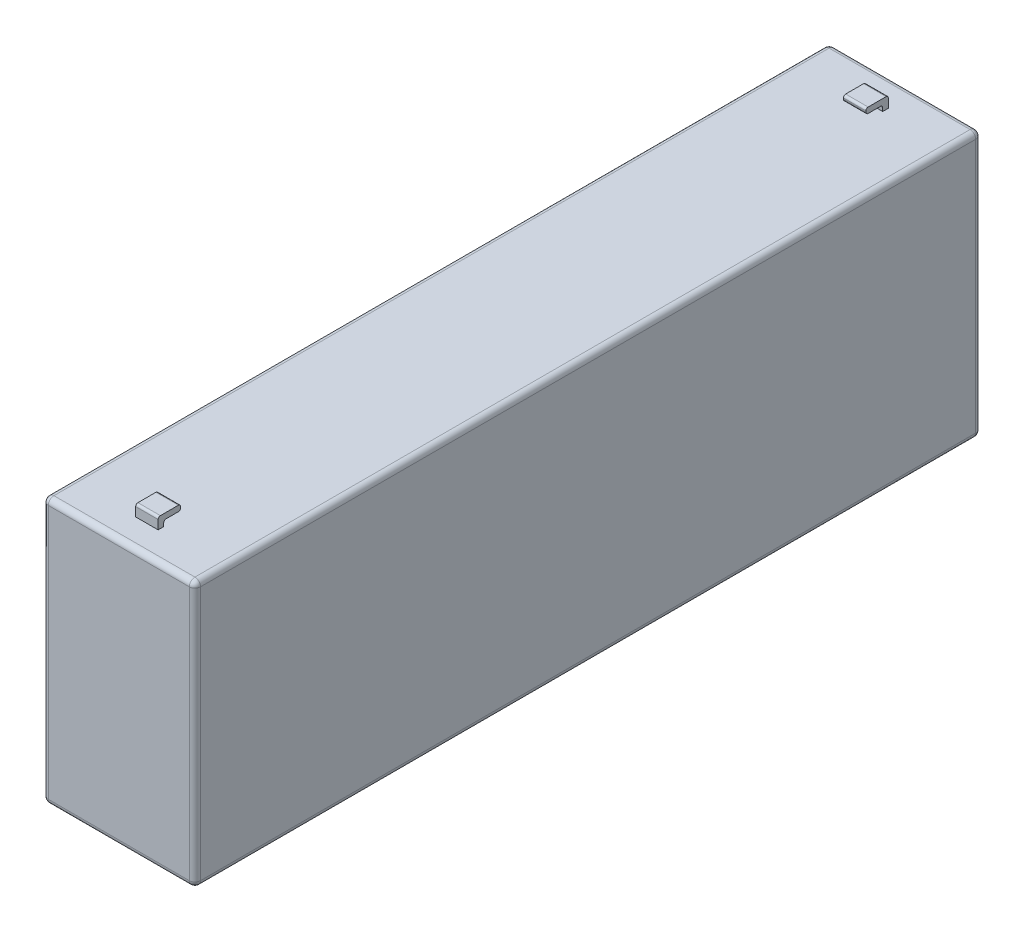
SolidWorks part; units mm, degrees
material "Rubber"
ref_plane "Front Plane" through (0, 0, 0) normal (0, 0, 1) x (1, 0, 0)
ref_plane "Top Plane" through (0, 0, 0) normal (0, 1, 0) x (1, 0, 0)
ref_plane "Right Plane" through (0, 0, 0) normal (1, 0, 0) x (0, 0, -1)
sketch "Sketch1" plane through (0, 0, 0) normal (0, 1, 0) x (1, 0, 0)
  line L1 (17.2085, -88.9) -> (-17.2085, -88.9)
  line L2 (17.2085, -88.9) -> (17.2085, 88.9)
  line L3 (17.2085, 88.9) -> (-17.2085, 88.9)
  line L4 (-17.2085, -88.9) -> (-17.2085, 88.9)
  line L5 (17.2085, -88.9) -> (-17.2085, 88.9) construction
  line L6 (17.2085, 88.9) -> (-17.2085, -88.9) construction
  point P0 (0, 0)
  dimension "D1" = 177.8
  dimension "D2" = 34.417
extrude "Boss-Extrude1" add sketch "Sketch1" along normal blind 60.071
fillet "Fillet1" radius 1.27 8 edges at (0, 0, 88.9) (17.2085, 0, 0) (0, 0, -88.9) (-17.2085, 0, 0) (0, 60.071, -88.9) (17.2085, 60.071, 0) (0, 60.071, 88.9) (-17.2085, 60.071, 0)
fillet "Fillet2" radius 1.27 12 edges at (-16.8365, 59.699, -88.528) (-16.8365, 0.372, -88.528) (16.8365, 59.699, -88.528) (16.8365, 0.372, -88.528) (16.8365, 59.699, 88.528) (16.8365, 0.372, 88.528) (-16.8365, 59.699, 88.528) (-16.8365, 0.372, 88.528) (-17.2085, 30.0355, -88.9) (17.2085, 30.0355, -88.9) (17.2085, 30.0355, 88.9) (-17.2085, 30.0355, 88.9)
sketch "Sketch2" plane through (0, 0, 0) normal (1, 0, 0) x (0, 0, -1)
  line L0 (-82.55, 60.071) -> (-82.55, 62.103)
  line L1 (-87.63, 60.071) -> (87.63, 60.071) construction
  line L2 (-82.042, 62.611) -> (-77.978, 62.611)
  line L3 (-81.28, 60.071) -> (-81.28, 60.833)
  line L4 (-80.772, 61.341) -> (-77.978, 61.341)
  line L5 (-82.55, 60.071) -> (-81.28, 60.071)
  line L6 (-88.9, 1.27) -> (-88.9, 58.801) construction
  line L7 (-77.47, 61.849) -> (-77.47, 62.103)
  line L8 (-82.55, 62.611) -> (-77.47, 62.611) construction
  line L9 (-81.28, 61.341) -> (-77.47, 61.341) construction
  line L10 (-81.28, 60.071) -> (-81.28, 61.341) construction
  line L11 (-82.55, 60.071) -> (-82.55, 62.611) construction
  arc A0 (-77.978, 62.611) -> (-77.47, 62.103) centre (-77.978, 62.103) cw
  arc A1 (-77.978, 61.341) -> (-77.47, 61.849) centre (-77.978, 61.849) ccw
  arc A2 (-81.28, 60.833) -> (-80.772, 61.341) centre (-80.772, 60.833) cw
  arc A3 (-82.55, 62.103) -> (-82.042, 62.611) centre (-82.042, 62.103) cw
  point P13 (-77.47, 62.611)
  dimension "D5" = 0.508
  dimension "D1" = 5.08
  dimension "D2" = 2.54
  dimension "D3" = 6.35
  dimension "D4" = 1.27
extrude "Boss-Extrude2" add sketch "Sketch2" along normal mid plane 5.08
mirror "Mirror1" about plane through (0, 0, 0) normal (0, 0, 1) of "Boss-Extrude2"
